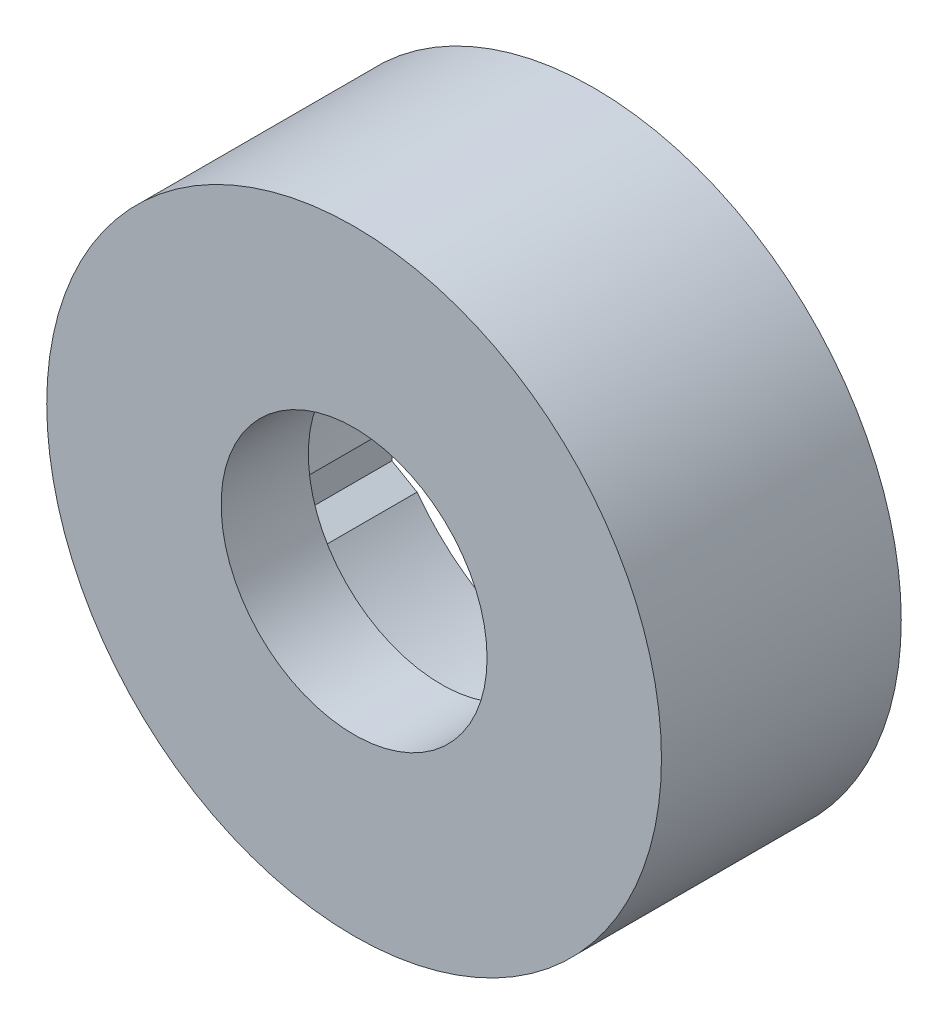
SolidWorks part; units mm, degrees
ref_plane "Front Plane" through (0, 0, 0) normal (0, 0, 1) x (1, 0, 0)
ref_plane "Top Plane" through (0, 0, 0) normal (0, 1, 0) x (1, 0, 0)
ref_plane "Right Plane" through (0, 0, 0) normal (1, 0, 0) x (0, 0, -1)
sketch "Sketch1" plane through (0, 0, 0) normal (0, 0, 1) x (1, 0, 0)
  circle A2 centre (0, 0) radius 3.05
  circle A3 centre (0, 0) radius 3.05
  circle A4 centre (0, 0) radius 7.05
  circle A5 centre (0, 0) radius 5.05
  circle A6 centre (0, 0) radius 5.05
  dimension "D1" = 0.05
  dimension "D2" = 0.05
  dimension "D3" = 2
extrude "Boss-Extrude1" add sketch "Sketch1" along normal blind 2 contours A4 A6 | A6 A3 region at (-6.8506, 0, 0) region at (-4.9072, 0, 0)
extrude "Boss-Extrude2" add sketch "Sketch1<3>" against normal blind 3.5 contours A4 A6 region at (-6.8506, 0, 0)
sketch "Sketch1<3>" plane through (0, 0, 0) normal (0, 0, 1) x (1, 0, 0) same geometry as "Sketch1"
sketch "Sketch2" plane through (0, 0, -3.5) normal (0, 0, -1) x (-1, 0, 0)
  line L1 (0, 5.35) -> (-4.6332, 2.675)
  line L2 (-4.6332, 2.675) -> (-4.6332, -2.675)
  line L3 (-4.6332, -2.675) -> (0, -5.35)
  line L4 (0, -5.35) -> (4.6332, -2.675)
  line L5 (4.6332, -2.675) -> (4.6332, 2.675)
  line L6 (4.6332, 2.675) -> (0, 5.35)
  circle A0 centre (0, 0) radius 4.6332 construction
  circle A1 centre (0, 0) radius 5.05 construction
  circle A2 centre (0, 0) radius 5.05
  circle M7 centre (0, 0) radius 5.05
  dimension "D1" = 0.3
extrude "Cut-Extrude1" cut sketch "Sketch2" against normal up to surface (3.5 mm away) contours L6 L1 M7 | L5 L6 M7 | L1 L2 M7 | L2 L3 M7 | L3 L4 M7 | L4 L5 M7 region at (0, 5.1429, -3.5) region at (4.4539, 2.5714, -3.5) region at (-4.4539, 2.5714, -3.5) region at (4.4539, -2.5714, -3.5) region at (-4.4539, -2.5714, -3.5) region at (0, -5.1429, -3.5) up to face at (3.05, 0, 0)
